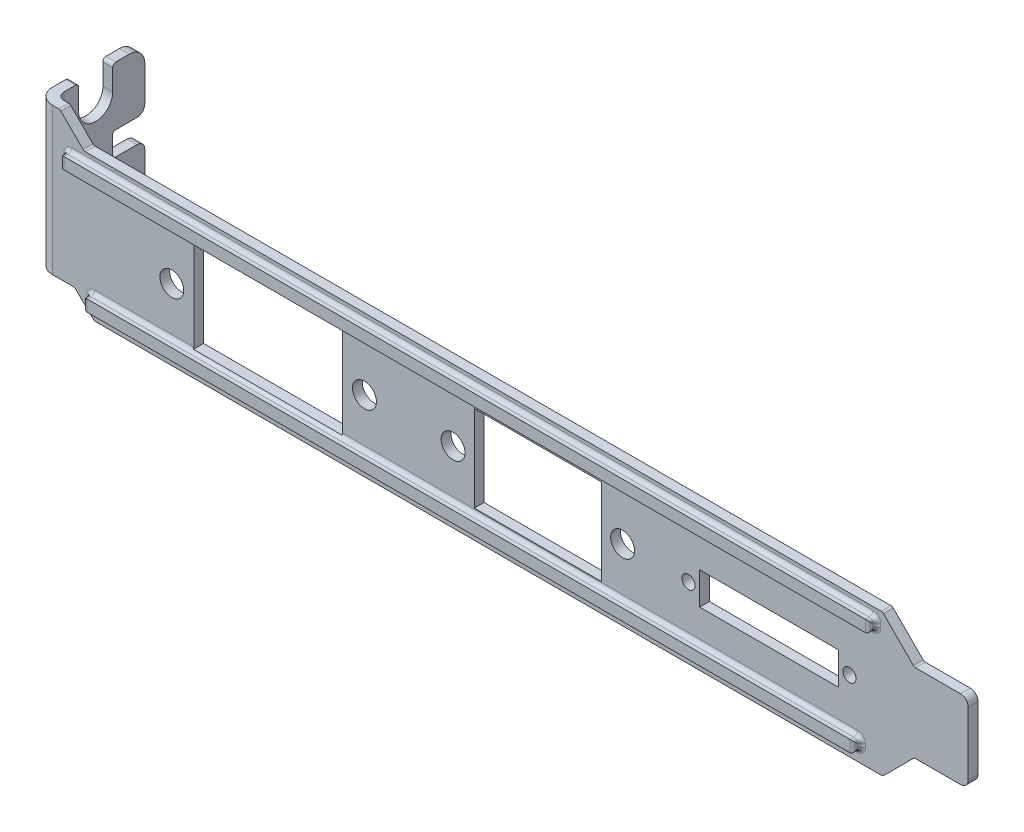
SolidWorks part; units mm, degrees
ref_plane "Front Plane" through (0, 0, 0) normal (0, 0, 1) x (1, 0, 0)
ref_plane "Top Plane" through (0, 0, 0) normal (0, 1, 0) x (1, 0, 0)
ref_plane "Right Plane" through (0, 0, 0) normal (1, 0, 0) x (0, 0, -1)
sketch "Sketch1" plane through (0, 0, 0) normal (0, 0, 1) x (1, 0, 0)
  line L0 (0, 2.48) -> (4.88, 2.48)
  line L5 (7.45, 0) -> (109.76, 0)
  line L6 (0, 2.48) -> (0, 21.53)
  line L7 (6.11, 18.42) -> (109.73, 18.42)
  line L8 (113.85, 4.09) -> (113.85, 14.3) construction
  line L9 (4.88, 2.48) -> (7.45, 0)
  line L10 (109.76, 0) -> (113.85, 4.09)
  line L11 (109.73, 18.42) -> (113.85, 14.3)
  line L12 (6.11, 18.42) -> (3, 21.53)
  line L13 (3, 21.53) -> (0, 21.53)
  line L16 (113.85, 14.3) -> (120.85, 14.3)
  line L18 (113.85, 4.09) -> (120.85, 4.09)
  line L19 (120.85, 14.3) -> (120.85, 4.09)
  dimension "D1" = 7.45
  dimension "D2" = 2.48
  dimension "D3" = 4.88
  dimension "D4" = 106.4
  dimension "D5" = 135
  dimension "D6" = 4.09
  dimension "D7" = 10.21
  dimension "D8" = 135
  dimension "D9" = 18.42
  dimension "D10" = 19.05
  dimension "D11" = 135
  dimension "D12" = 3
  dimension "D13" = 7
extrude "Boss-Extrude1" add sketch "Sketch1" along normal blind 1.27
sketch "Sketch8" plane through (0, 0, 0) normal (0, 0, -1) x (-1, 0, 0)
  line L0 (0, 2.48) -> (-4.88, 2.48) construction
  line L1 (0, 21.53) -> (-1.27, 21.53)
  line L2 (0, 21.53) -> (0, 2.48)
  line L3 (0, 2.48) -> (-1.27, 2.48)
  line L4 (-1.27, 21.53) -> (-1.27, 2.48)
  dimension "D1" = 1.27
extrude "Boss-Extrude3" add sketch "Sketch8" along normal blind 11.454
sketch "Sketch9" plane through (0, 0, 0) normal (-1, 0, 0) x (0, 0, 1)
  line L0 (1.27, 21.53) -> (1.27, 2.48) construction
  line L1 (-7.29, 18.35) -> (-7.29, 21.53)
  line L2 (1.27, 21.53) -> (-11.454, 21.53) construction
  line L3 (-7.29, 21.53) -> (-2.87, 21.53)
  line L4 (-2.87, 21.53) -> (-2.87, 18.35)
  line L5 (-11.454, 2.48) -> (-11.454, 21.53) construction
  line L6 (-11.454, 13.91) -> (-7.264, 13.91)
  line L7 (-11.454, 13.91) -> (-11.454, 10.86)
  line L8 (-11.454, 10.86) -> (-7.264, 10.86)
  line L9 (-7.264, 13.91) -> (-7.264, 10.86)
  arc A0 (-7.29, 18.35) -> (-2.87, 18.35) centre (-5.08, 18.35) ccw
  dimension "D3" = 2.21
  dimension "D1" = 6.35
  dimension "D2" = 3.18
  dimension "D4" = 4.19
  dimension "D5" = 3.05
  dimension "D6" = 7.62
extrude "Cut-Extrude6" cut sketch "Sketch9" against normal up to next
ref_plane "Plane1" through (0, 9.21, 0) normal (0, -1, 0) x (-1, 0, 0)
sketch "Sketch10" plane through (0, 0, 1.27) normal (0, 0, -1) x (-1, 0, 0)
  line L1 (-7, 1.5) -> (-107, 1.5)
  line L2 (-7, 1.5) -> (-7, 3)
  line L3 (-7, 3) -> (-107, 3)
  line L4 (-107, 1.5) -> (-107, 3)
  line L5 (-109, 16) -> (-4, 16)
  line L6 (-109, 16) -> (-109, 17.5)
  line L7 (-109, 17.5) -> (-4, 17.5)
  line L8 (-4, 16) -> (-4, 17.5)
  dimension "D1" = 1.5
  dimension "D2" = 1.5
  dimension "D3" = 7
  dimension "D4" = 100
  dimension "D5" = 4
  dimension "D6" = 16
  dimension "D7" = 105
extrude "Boss-Extrude4" add sketch "Sketch10" against normal blind 1
sketch "Sketch3" plane through (0, 0, 1.27) normal (0, 0, 1) x (1, 0, 0)
  line L1 (17.5, 9.21) -> (42.5, 9.21) construction
  line L2 (20.35, 3.285) -> (39.65, 3.285)
  line L3 (20.35, 3.285) -> (20.35, 15.135)
  line L4 (20.35, 15.135) -> (39.65, 15.135)
  line L5 (39.65, 3.285) -> (39.65, 15.135)
  line L6 (20.35, 3.285) -> (39.65, 15.135) construction
  line L7 (20.35, 15.135) -> (39.65, 3.285) construction
  line L8 (0, 21.53) -> (0, 2.48) construction
  line L9 (-0.6985, 9.21) -> (0.6985, 9.21) construction
  circle A0 centre (17.5, 9.21) radius 1.55
  circle A1 centre (42.5, 9.21) radius 1.55
  point P4 (30, 9.21)
  point P8 (30, 9.21)
  dimension "D2" = 3.1
  dimension "D3" = 25
  dimension "D1" = 30
  dimension "D4" = 11.85
  dimension "D5" = 19.3
extrude "XT60 cutout" cut sketch "Sketch3" against normal through all
sketch "Sketch5" plane through (0, 0, 1.27) normal (0, 0, 1) x (1, 0, 0)
  line L0 (-0.6985, 9.21) -> (0.6985, 9.21) construction
  line L1 (54, 9.21) -> (76, 9.21) construction
  line L2 (56.75, 3.61) -> (73.25, 3.61)
  line L3 (56.75, 3.61) -> (56.75, 14.81)
  line L4 (56.75, 14.81) -> (73.25, 14.81)
  line L5 (73.25, 3.61) -> (73.25, 14.81)
  line L6 (56.75, 3.61) -> (73.25, 14.81) construction
  line L7 (56.75, 14.81) -> (73.25, 3.61) construction
  circle A0 centre (54, 9.21) radius 1.55
  circle A1 centre (76, 9.21) radius 1.55
  point P4 (65, 9.21)
  point P8 (65, 9.21)
  dimension "D2" = 3.1
  dimension "D3" = 22
  dimension "D1" = 65
  dimension "D4" = 11.2
  dimension "D5" = 16.5
extrude "Cut-Extrude4" cut sketch "Sketch5" against normal through all and the other way through all
sketch "Sketch6" plane through (0, 0, 1.27) normal (0, 0, 1) x (1, 0, 0)
  line L0 (84.56, 9.21) -> (105.44, 9.21) construction
  line L1 (86, 7.11) -> (104, 7.11)
  line L2 (86, 7.11) -> (86, 11.31)
  line L3 (86, 11.31) -> (104, 11.31)
  line L4 (104, 7.11) -> (104, 11.31)
  line L5 (86, 7.11) -> (104, 11.31) construction
  line L6 (86, 11.31) -> (104, 7.11) construction
  line L7 (-0.6985, 9.21) -> (0.6985, 9.21) construction
  circle A0 centre (105.44, 9.21) radius 0.85
  circle A1 centre (84.56, 9.21) radius 0.85
  point P0 (95, 9.21)
  point P12 (95, 9.21)
  dimension "D4" = 1.7
  dimension "D1" = 18
  dimension "D2" = 4.2
  dimension "D3" = 95
  dimension "D5" = 20.88
extrude "Cut-Extrude5" cut sketch "Sketch6" against normal through all
fillet "Fillet1" radius 0.4 12 edges at (109.76, 0, 0.635) (113.85, 4.09, 0.635) (113.85, 14.3, 0.635) (109.73, 18.42, 0.635) (4.88, 2.48, 0.635) (7.45, 0, 0.635) (3, 21.53, 0.635) (6.11, 18.42, 0.635) (0.635, 21.53, -7.29) (0.635, 21.53, -2.87) (0.635, 10.86, -7.264) (0.635, 13.91, -7.264)
fillet "Fillet2" radius 1 5 edges at (0.635, 13.91, -11.454) (0.635, 10.86, -11.454) (120.85, 14.3, 0.635) (120.85, 4.09, 0.635) (1.27, 12.005, 0)
fillet "Fillet3" radius 2 3 edges at (0, 12.005, 1.27) (0.635, 2.48, -11.454) (0.635, 21.53, -11.454)
fillet "Fillet4" radius 0.5 20 edges at (109, 17.5, 1.77) (109, 16.75, 2.27) (109, 16, 1.77) (107, 3, 1.77) (107, 2.25, 2.27) (107, 1.5, 1.77) (4, 16, 1.77) (4, 16.75, 2.27) (4, 17.5, 1.77) (7, 1.5, 1.77) (7, 2.25, 2.27) (7, 3, 1.77) (56.5, 17.5, 1.27) (56.5, 16, 1.27) (57, 3, 1.27) (57, 1.5, 1.27) (109, 16.75, 1.27) (107, 2.25, 1.27) (4, 16.75, 1.27) (7, 2.25, 1.27)
